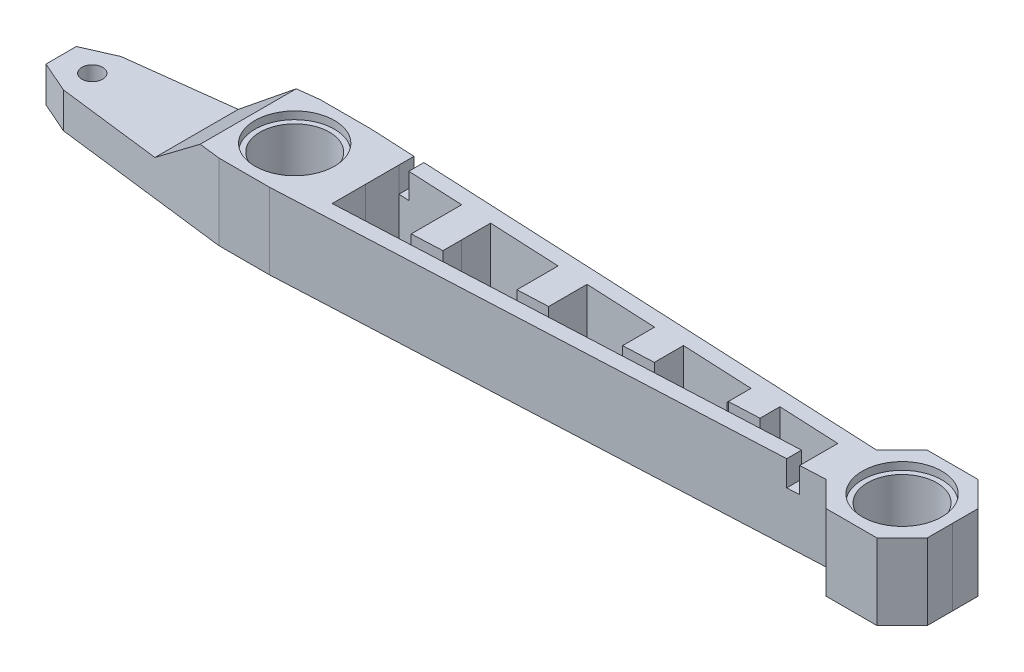
SolidWorks part; units mm, degrees
note: The reader was unsure of these and kept them because the rebuilt part matched: shared geometry of "Sketch1<3>", "Sketch1<4>".
ref_plane "Front Plane" through (0, 0, 0) normal (0, 0, 1) x (1, 0, 0)
ref_plane "Top Plane" through (0, 0, 0) normal (0, 1, 0) x (1, 0, 0)
ref_plane "Right Plane" through (0, 0, 0) normal (1, 0, 0) x (0, 0, -1)
sketch "Sketch1" plane through (0, 0, 0) normal (0, 1, 0) x (1, 0, 0)
  line L0 (-78.7123, 0) -> (95.1777, 0) construction
  line L1 (91.2869, -0.0008) -> (91.2869, -5.0008)
  line L8 (91.2869, -5.0008) -> (86.2877, -10)
  line L9 (86.2877, -10) -> (76.2877, -10)
  line L10 (76.2877, -10) -> (71.2884, -5.0008)
  line L11 (-43.7123, -10) -> (-33.7123, -10)
  line L12 (-33.7123, -10) -> (71.2884, -5.0008)
  line L13 (-78.7123, -5.7025) -> (-43.7123, -10)
  line L14 (-78.7123, -5.7025) -> (-84.854, -3)
  line L15 (-84.854, -3) -> (-84.854, 0)
  line L16 (-84.854, 0) -> (91.2869, -0.0008)
  line L17 (91.2869, -0.0008) -> (91.287, 4.9992)
  line L18 (91.287, 4.9992) -> (86.2878, 9.9985)
  line L19 (76.2878, 9.9986) -> (71.2885, 4.9994)
  line L20 (86.2878, 9.9985) -> (76.2878, 9.9986)
  line L21 (-33.7122, 9.9996) -> (71.2885, 4.9994)
  line L22 (-43.7122, 9.9996) -> (-33.7122, 9.9996)
  line L23 (-78.7123, 5.7025) -> (-43.7122, 9.9996)
  line L24 (-78.7123, 5.7025) -> (-84.854, 3)
  line L25 (-84.854, 3) -> (-84.854, 0)
  circle A0 centre (-78.7123, 0) radius 2.05
  circle A1 centre (-38.7123, 0) radius 7.85
  circle A2 centre (81.2877, 0) radius 6.85
  circle A3 centre (81.2877, 0) radius 7.85
  circle A4 centre (-38.7123, 0) radius 6.85
  point P15 (81.2877, -10)
  point P18 (-38.7123, -10)
  dimension "D1" = 160
  dimension "D3" = 4.1
  dimension "D4" = 15.7
  dimension "D5" = 13.7
  dimension "D6" = 15.7
  dimension "D7" = 13.7
  dimension "D2" = 40
  dimension "D8" = 10
  dimension "D9" = 5
  dimension "D10" = 7.07
  dimension "D11" = 135
  dimension "D12" = 10
  dimension "D13" = 7.07
  dimension "D14" = 135
  dimension "D15" = 10
  dimension "D16" = 173
  dimension "D17" = 3
  dimension "D18" = 6.71
extrude "Boss-Extrude1" add sketch "Sketch1" along normal blind 15 contours A0 L0 A1 A3 L17 L18 L20 L19 L21 L22 L23 L24 L25 L16 | A3 L16 A1 A0 L15 L14 L13 L11 L12 L10 L9 L8 L1 | A1 L0 A4 | A4 L16 A1 | A3 L0 A2 | L16 A3 A2
extrude "Cut-Extrude1" cut sketch "Sketch1<3>" along normal blind 1.5 contours A1 | A3
sketch "Sketch1<3>" plane through (0, 0, 0) normal (0, 1, 0) x (1, 0, 0) same geometry as "Sketch1"
extrude "Cut-Extrude2" cut sketch "Sketch1<4>" against normal blind 1.5 from offset 15 contours A1 | A3
sketch "Sketch1<4>" plane through (0, 0, 0) normal (0, 1, 0) x (1, 0, 0) same geometry as "Sketch1"
sketch "Sketch2" plane through (0, 15, 0) normal (0, 1, 0) x (1, 0, 0)
  line L0 (-38.7123, -0.0004) -> (81.2877, 0) construction
  line L1 (66.2877, 0) -> (66.2877, -2.3013)
  line L2 (-24.7123, -6.6003) -> (-11.7123, -5.9862)
  line L3 (-24.7123, -6.6003) -> (-24.7123, -0.0003)
  line L4 (-11.7123, -0.0003) -> (-11.7123, -5.9862)
  line L5 (-5.7123, -0.0003) -> (-5.7123, -5.7027)
  line L6 (8.2877, -0.0002) -> (8.2877, -5.0413)
  line L7 (14.2877, -0.0002) -> (14.2877, -4.7579)
  line L8 (28.2877, -0.0002) -> (28.2877, -4.0965)
  line L9 (34.2877, -0.0002) -> (34.2877, -3.813)
  line L10 (48.2877, -0.0002) -> (48.2877, -3.1516)
  line L11 (54.2877, -0.0002) -> (54.2877, -2.8682)
  line L12 (-5.7123, -5.7027) -> (8.2877, -5.0413)
  line L13 (14.2877, -4.7579) -> (28.2877, -4.0965)
  line L14 (34.2877, -3.813) -> (48.2877, -3.1516)
  line L15 (14.2877, -0.0002) -> (14.2877, -5.0413) construction
  line L16 (28.2877, -0.0002) -> (28.2877, -5.0413) construction
  line L17 (54.2877, -2.8682) -> (66.2877, -2.3013)
  line L18 (34.2877, -0.0002) -> (34.2877, -5.0413) construction
  line L19 (48.2877, -0.0002) -> (48.2877, -5.0413) construction
  line L20 (54.2877, 2.868) -> (66.2877, 2.3012)
  line L21 (54.2877, -0.0002) -> (54.2877, -5.0413) construction
  line L22 (54.2877, 0.0001) -> (54.2877, 2.868)
  line L23 (48.2877, 0) -> (48.2876, 3.1514)
  line L24 (66.2877, 0) -> (66.2877, 2.3012)
  line L25 (34.2876, 3.8127) -> (48.2876, 3.1514)
  line L26 (14.2876, 4.7574) -> (28.2876, 4.0961)
  line L27 (34.2877, -0.0001) -> (34.2876, 3.8127)
  line L28 (28.2877, -0.0001) -> (28.2876, 4.0961)
  line L29 (14.2877, -0.0002) -> (14.2876, 4.7574)
  line L30 (8.2877, -0.0002) -> (8.2876, 5.0409)
  line L31 (-5.7124, 5.7022) -> (8.2876, 5.0409)
  line L32 (-5.7123, -0.0003) -> (-5.7124, 5.7022)
  line L33 (-11.7123, -0.0003) -> (-11.7124, 5.9856)
  line L34 (-24.7124, 6.5997) -> (-11.7124, 5.9856)
  line L35 (-24.7124, 6.5997) -> (-24.7123, -0.0003)
  line L36 (-24.7124, 6.5997) -> (-24.7124, 9.571)
  line L38 (-24.7124, 9.571) -> (-22.6647, 9.4735)
  line L39 (-22.6647, 9.4735) -> (-22.6647, 6.5029)
  line L40 (66.2877, -2.3013) -> (66.2877, -5.2388)
  line L41 (-33.7123, -10) -> (71.2884, -5.0008) construction
  line L42 (66.2877, -5.2388) -> (64.24, -5.3363)
  line L43 (64.24, -5.3363) -> (64.24, -2.398)
  line L44 (-11.7123, -3.9862) -> (54.2877, -1.0682) construction
  line L45 (-11.7123, -3.9862) -> (-5.7123, -3.7209)
  line L46 (8.2877, -3.1019) -> (14.2877, -2.8367)
  line L47 (48.2944, -1.3332) -> (54.2877, -1.0682)
  line L48 (28.2877, -2.2177) -> (34.2877, -1.9524)
  line L49 (-11.7123, -5.9862) -> (66.2877, -2.3013)
  line L50 (48.2877, -3.1516) -> (54.2877, -2.8682)
  line L51 (54.2877, -2.8682) -> (48.2877, -3.1516)
  point P6 (66.2877, -1.1507)
  point P55 (66.2877, -1.5)
  point P56 (-11.7123, -3.9862)
  point P57 (54.2877, -1.0682)
  dimension "D1" = 15
  dimension "D2" = 6.6
  dimension "D3" = 2.3012
  dimension "D4" = 14
  dimension "D5" = 13
  dimension "D6" = 6
  dimension "D7" = 14
  dimension "D8" = 6
  dimension "D13" = 1.8
  dimension "D14" = 2
  dimension "D9" = 14
  dimension "D10" = 6
  dimension "D11" = 14
  dimension "D12" = 6
extrude "Cut-Extrude18" cut sketch "Sketch2" against normal blind 15 contours L34 L35 L3 L2 L4 L33 | L32 L5 L12 L6 L30 L31
sketch "Sketch5" plane through (0, 15, 0) normal (0, 1, 0) x (1, 0, 0)
  line L0 (14.2877, -4.7579) -> (14.2876, 4.7574)
  line L1 (14.2876, 4.7574) -> (28.2876, 4.0961)
  line L2 (28.2876, 4.0961) -> (28.2877, -4.0965)
  line L3 (28.2877, -4.0965) -> (14.2877, -4.7579)
  line L4 (34.2876, 3.8127) -> (48.2876, 3.1514)
  line L5 (48.2876, 3.1514) -> (48.2877, -3.1516)
  line L6 (48.2877, -3.1516) -> (34.2877, -3.813)
  line L7 (34.2877, -3.813) -> (34.2876, 3.8127)
  line L8 (54.2877, 2.868) -> (66.2877, 2.3012)
  line L9 (66.2877, 2.3012) -> (66.2877, -2.3013)
  line L10 (66.2877, -2.3013) -> (54.2877, -2.8682)
  line L11 (54.2877, -2.8682) -> (54.2877, 2.868)
extrude "Cut-Extrude19" cut sketch "Sketch5" against normal blind 15
sketch "Sketch6" plane through (0, 15, 0) normal (0, 1, 0) x (1, 0, 0)
  line L0 (-24.7124, 9.571) -> (-22.6647, 9.4735)
  line L1 (-22.6647, 9.4735) -> (-22.6647, 6.5029)
  line L2 (-22.6647, 6.5029) -> (-24.7124, 6.5997)
  line L3 (-24.7124, 6.5997) -> (-24.7124, 9.571)
  line L4 (64.24, -2.398) -> (66.2877, -2.3013)
  line L5 (66.2877, -2.3013) -> (66.2877, -5.2388)
  line L6 (66.2877, -5.2388) -> (64.24, -5.3363)
  line L8 (54.2877, -1.0682) -> (54.2877, -2.8682)
  line L9 (54.2877, -2.8682) -> (48.2877, -3.1516)
  line L10 (48.2877, -3.1516) -> (48.2877, -1.5759)
  line L11 (48.2877, -0.0002) -> (48.2877, -3.1516) construction
  line L12 (48.2877, -1.5759) -> (48.2944, -1.3332)
  line L13 (48.2944, -1.3332) -> (54.2877, -1.0682)
  line L14 (34.2877, -1.9524) -> (28.2877, -2.2177)
  line L15 (28.2877, -2.2177) -> (28.2877, -4.0965)
  line L16 (28.2877, -4.0965) -> (34.2877, -3.813)
  line L17 (34.2877, -3.813) -> (34.2877, -1.9524)
  line L18 (8.2877, -3.1019) -> (14.2877, -2.8367)
  line L19 (14.2877, -2.8367) -> (14.2877, -4.7579)
  line L20 (14.2877, -4.7579) -> (8.2877, -5.0413)
  line L21 (8.2877, -5.0413) -> (8.2877, -3.1019)
  line L22 (-5.7123, -3.7209) -> (-11.7123, -3.9862)
  line L23 (-11.7123, -3.9862) -> (-11.7123, -5.9862)
  line L24 (-11.7123, -5.9862) -> (-5.7123, -5.7027)
  line L25 (-5.7123, -5.7027) -> (-5.7123, -3.7209)
  line L26 (64.24, -2.398) -> (63.8431, -2.4168)
  line L27 (54.2877, -2.8682) -> (66.2877, -2.3013) construction
  line L28 (63.8431, -2.4168) -> (63.8431, -5.3552)
  line L29 (-33.7123, -10) -> (71.2884, -5.0008) construction
  line L30 (63.8431, -5.3552) -> (64.24, -5.3363)
extrude "Cut-Extrude20" cut sketch "Sketch6" against normal blind 5
sketch "Sketch8" plane through (0, 0, 10) normal (0, 0, 1) x (1, 0, 0)
  line L0 (-47.904, 0) -> (-58.104, 8)
  line L1 (-43.7123, 0) -> (-33.7123, 0) construction
  line L2 (-58.104, 8) -> (-84.854, 8)
  line L3 (-84.854, 15) -> (-84.854, 0) construction
  line L4 (-84.854, 8) -> (-84.854, 0)
  line L5 (-84.854, 0) -> (-47.904, 0)
  dimension "D1" = 26.75
  dimension "D2" = 8
  dimension "D3" = 10.2
extrude "Cut-Extrude21" cut sketch "Sketch8" against normal blind 25
sketch "Sketch9" plane through (0, 8, 0) normal (0, -1, 0) x (1, 0, 0)
  line L0 (-84.854, 3) -> (-84.854, -3)
  line L1 (-84.854, -3) -> (-78.7123, -5.7025)
  line L2 (-78.7123, -5.7025) -> (-47.0328, -9.592)
  line L3 (-84.854, 3) -> (-78.7123, 5.7025)
  line L4 (-78.7123, 5.7025) -> (-47.3808, 9.5496)
  line L5 (-47.3808, 9.5496) -> (-47.0328, -9.592)
  circle A0 centre (-78.7123, 0) radius 2.05
extrude "Boss-Extrude2" add sketch "Sketch9" along normal blind 8
sketch "Sketch10" plane through (0.0001, 0, -9.9993) normal (0, 0, -1) x (-1, 0, 0)
  line L0 (47.904, 15) -> (58.104, 7)
  line L1 (38.7123, 15) -> (-81.2877, 15) construction
  line L2 (58.104, 7) -> (84.854, 7)
  line L3 (84.854, 0) -> (84.854, 8) construction
  line L4 (84.854, 7) -> (84.854, 15)
  line L5 (84.854, 15) -> (47.904, 15)
  dimension "D1" = 8
  dimension "D2" = 26.75
  dimension "D3" = 10.2
extrude "Cut-Extrude22" cut sketch "Sketch10" against normal blind 30
